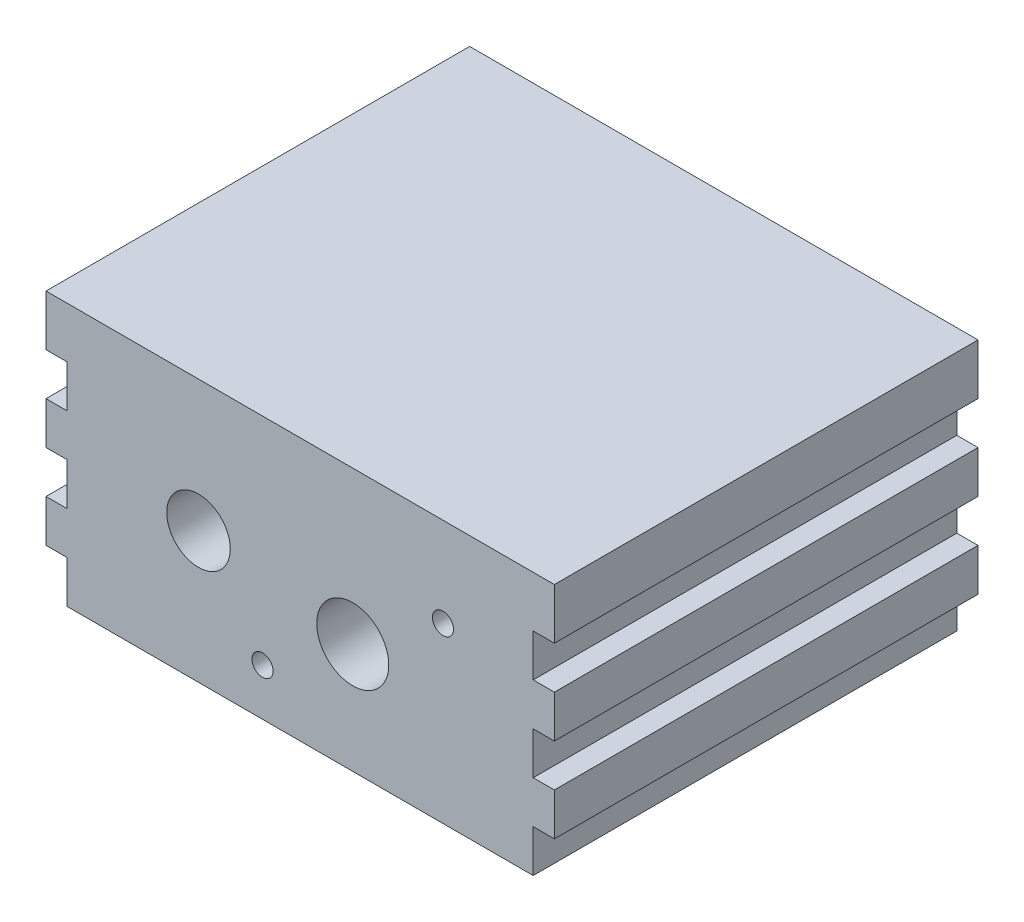
SolidWorks part; units mm, degrees
ref_plane "정면" through (0, 0, 0) normal (0, 0, 1) x (1, 0, 0)
ref_plane "윗면" through (0, 0, 0) normal (0, 1, 0) x (1, 0, 0)
ref_plane "우측면" through (0, 0, 0) normal (1, 0, 0) x (0, 0, -1)
sketch "스케치2" plane through (0, 0, 0) normal (0, 0, 1) x (1, 0, 0)
  line L0 (-6.0717, -5) -> (65.5766, -5) construction
  line L1 (-60, -31) -> (60, -31)
  line L2 (-60, -31) -> (-60, 31)
  line L3 (-60, 31) -> (60, 31)
  line L4 (60, -31) -> (60, 31)
  line L5 (-60, -31) -> (60, 31) construction
  line L6 (-60, 31) -> (60, -31) construction
  line L7 (-15.8273, -24.7708) -> (37.7136, 12.7189) construction
  circle A0 centre (12.4083, -5) radius 8.5
  circle A1 centre (-24, 0) radius 7.5
  circle A2 centre (33.7062, 9.913) radius 2.5
  circle A3 centre (-8.8897, -19.913) radius 2.5
  point P0 (0, 0)
  dimension "D5" = 17
  dimension "D8" = 15
  dimension "D9" = 35
  dimension "D10" = 5
  dimension "D1" = 62
  dimension "D2" = 120
  dimension "D3" = 36.75
  dimension "D4" = 36
  dimension "D6" = 31
  dimension "D7" = 36
  dimension "D11" = 26
  dimension "D12" = 26
extrude "보스-돌출1" add sketch "스케치2" along normal blind 100 contours L1 L4 L3 L2 A1 A0 region at (0.134, 0.1903, 0)
sketch "스케치3" plane through (0, 0, 100) normal (0, 0, 1) x (1, 0, 0)
  line L0 (-60, -31) -> (-60, 31) construction
  line L1 (-60, -21) -> (-55, -21)
  line L2 (-60, -21) -> (-60, -31)
  line L3 (-60, -31) -> (-55, -31)
  line L4 (-55, -21) -> (-55, -31)
  line L5 (-60, -31) -> (60, -31) construction
  dimension "D1" = 5
  dimension "D2" = 10
extrude "컷-돌출1" cut sketch "스케치3" against normal up to next
pattern_linear "선형 패턴1" count 3 spacing 20 along (0, 1, 0) of "컷-돌출1"
mirror "대칭 복사1" about plane through (0, 0, 0) normal (1, 0, 0) of "선형 패턴1"
